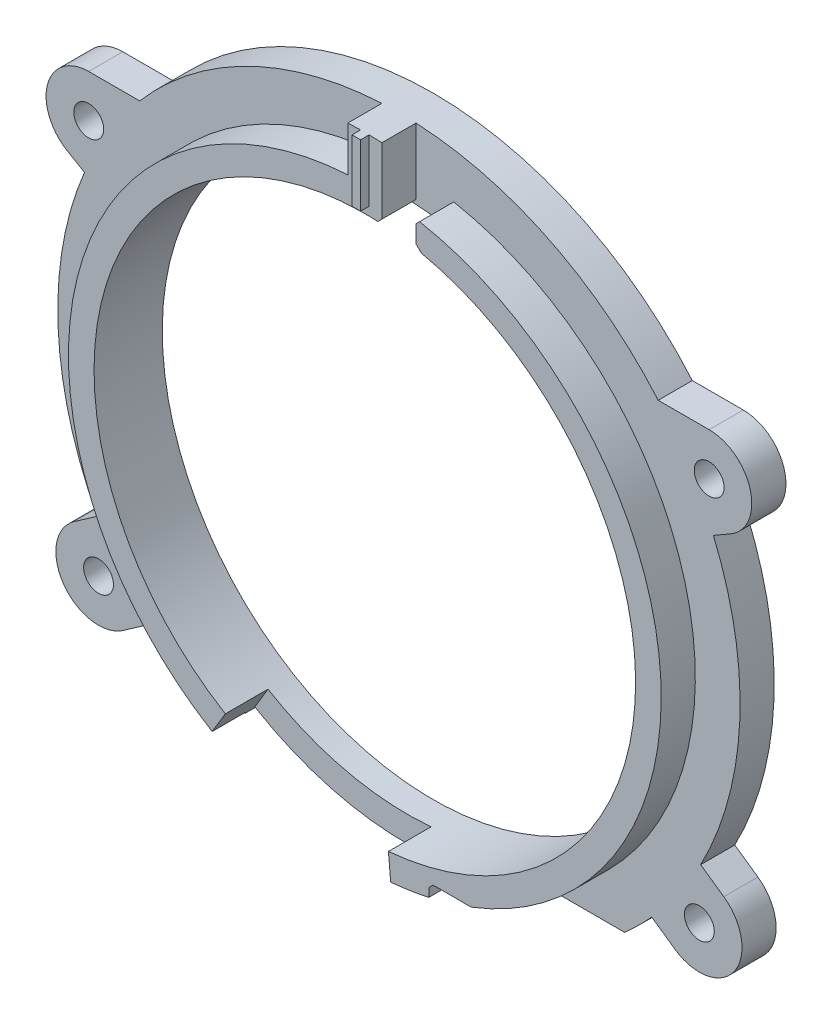
SolidWorks part; units mm, degrees
ref_plane "前视基准面" through (0, 0, 0) normal (0, 0, 1) x (1, 0, 0)
ref_plane "上视基准面" through (0, 0, 0) normal (0, 1, 0) x (1, 0, 0)
ref_plane "右视基准面" through (0, 0, 0) normal (1, 0, 0) x (0, 0, -1)
sketch "草图1" plane through (0, 0, 0) normal (0, 0, 1) x (1, 0, 0)
  circle A0 centre (0, 0) radius 31.75
  circle A1 centre (0, 0) radius 40
  dimension "D1" = 63.5
  dimension "D2" = 80
extrude "凸台-拉伸1" add sketch "草图1" along normal blind 4
sketch "草图2" plane through (0, 0, 4) normal (0, 0, 1) x (1, 0, 0)
  line L0 (0, 0) -> (0, -40) construction
  line L1 (0, 0) -> (-35.2235, -24.6638) construction
  line L2 (-38.0914, -20.568) -> (-35.377, -18.6673)
  line L3 (-32.3557, -28.7595) -> (-29.6412, -26.8589)
  line L4 (0, 0) -> (35.2235, -24.6638) construction
  line L5 (32.3557, -28.7595) -> (29.6412, -26.8589)
  line L6 (38.0914, -20.568) -> (35.377, -18.6673)
  circle A0 centre (0, 0) radius 40 construction
  circle A1 centre (-35.2235, -24.6638) radius 1.75
  arc A2 (-38.0914, -20.568) -> (-32.3557, -28.7595) centre (-35.2235, -24.6638) ccw
  arc A3 (-35.377, -18.6673) -> (-29.6412, -26.8589) centre (0, 0) ccw
  arc A4 (35.377, -18.6673) -> (29.6412, -26.8589) centre (0, 0) cw
  arc A5 (38.0914, -20.568) -> (32.3557, -28.7595) centre (35.2235, -24.6638) cw
  circle A6 centre (35.2235, -24.6638) radius 1.75
  dimension "D1" = 3.5
  dimension "D2" = 10
  dimension "D3" = 43
  dimension "D4" = 55
extrude "凸台-拉伸2" add sketch "草图2" against normal up to surface (4 mm away) up to face at (40, 0, 0)
sketch "草图3" plane through (0, 0, 4) normal (0, 0, 1) x (1, 0, 0)
  line L1 (-26.4575, -30) -> (-18.0278, -30)
  line L2 (18.0278, -30) -> (26.4575, -30)
  circle A2 centre (0, 0) radius 40 construction
  arc A3 (-26.4575, -30) -> (26.4575, -30) centre (0, 0) ccw
  circle A4 centre (0, 0) radius 35 construction
  arc A5 (18.0278, -30) -> (-18.0278, -30) centre (0, 0) cw
  dimension "D2" = 70
  dimension "D1" = 30
extrude "切除-拉伸2" cut sketch "草图3" against normal through all
sketch "草图4" plane through (0, 0, 4) normal (0, 0, 1) x (1, 0, 0)
  line L0 (0, 0) -> (0, 40) construction
  line L1 (-36.3731, 21) -> (0, 0) construction
  line L2 (-36.3731, 26) -> (-30.3974, 26)
  line L3 (-38.8731, 16.6699) -> (-36.8693, 15.513)
  line L4 (36.3731, 21) -> (0, 0) construction
  line L5 (38.8731, 16.6699) -> (36.8693, 15.513)
  line L6 (36.3731, 26) -> (30.3974, 26)
  circle A0 centre (0, 0) radius 40 construction
  circle A1 centre (-36.3731, 21) radius 1.75
  arc A2 (-36.3731, 26) -> (-38.8731, 16.6699) centre (-36.3731, 21) ccw
  arc A3 (-30.3974, 26) -> (-36.8693, 15.513) centre (0, 0) ccw
  arc A4 (30.3974, 26) -> (36.8693, 15.513) centre (0, 0) cw
  arc A5 (36.3731, 26) -> (38.8731, 16.6699) centre (36.3731, 21) cw
  circle A6 centre (36.3731, 21) radius 1.75
  arc M15 (35.377, -18.6673) -> (-35.377, -18.6673) centre (0, 0) ccw
  dimension "D1" = 3.5
  dimension "D2" = 10
  dimension "D3" = 42
  dimension "D4" = 60
extrude "凸台-拉伸3" add sketch "草图4" against normal up to surface (4 mm away) contours L2 A2 L3 A1 M15 | A6 L5 A5 L6 M15 region at (33.3852, 25.8482, 4) region at (-33.3852, 25.8482, 4) up to face at (0, -21.8221, 0)
sketch "草图5" plane through (0, 0, 4) normal (0, 0, -1) x (-1, 0, 0)
  circle A0 centre (0, 0) radius 31.75
  circle A1 centre (0, 0) radius 34.75
  circle A2 centre (0, 0) radius 31.75 construction
  dimension "D1" = 3
extrude "凸台-拉伸4" add sketch "草图5" against normal blind 4
sketch "草图6" plane through (0, 0, 4) normal (0, 0, 1) x (1, 0, 0)
  line L0 (-17.899, -29.7857) -> (-16.3538, -27.2143)
  line L2 (2.7672, -31.6292) -> (3.0287, -34.6178)
  line L3 (0, 0) -> (0, -35) construction
  circle A0 centre (0, 0) radius 31.75 construction
  arc A1 (-16.3538, -27.2143) -> (2.7672, -31.6292) centre (0, 0) ccw
  circle A2 centre (0, 0) radius 34.75 construction
  arc A3 (-17.899, -29.7857) -> (3.0287, -34.6178) centre (0, 0) ccw
  arc A4 (-18.0278, -30) -> (18.0278, -30) centre (0, 0) ccw construction
  dimension "D1" = 5
extrude "切除-拉伸3" cut sketch "草图6" along normal through all
sketch "草图7" plane through (0, 0, 4) normal (0, 0, 1) x (1, 0, 0)
  line L0 (-2, 39.95) -> (-2, 34.6924)
  line L1 (0, 40) -> (0, 0) construction
  line L2 (2, 39.95) -> (2, 34.6924)
  arc A0 (30.3974, 26) -> (-30.3974, 26) centre (0, 0) ccw construction
  arc A1 (3.0287, -34.6178) -> (-17.899, -29.7857) centre (0, 0) ccw construction
  arc A2 (2, 34.6924) -> (-2, 34.6924) centre (0, 0) ccw
  arc A3 (2, 39.95) -> (-2, 39.95) centre (0, 0) ccw
  dimension "D1" = 2
extrude "凸台-拉伸5" add sketch "草图7" along normal up to surface (4 mm away) up to face at (0.1831, 0.7929, 8)
sketch "草图8" plane through (0, 0, 8) normal (0, 0, 1) x (1, 0, 0)
  line L0 (-0.5, 39.9969) -> (-0.5, 31.7461)
  line L1 (0, 0) -> (0, 40) construction
  line L2 (0.5, 39.9969) -> (0.5, 31.7461)
  arc A0 (2, 39.95) -> (-2, 39.95) centre (0, 0) ccw construction
  arc A1 (2.7672, -31.6292) -> (-16.3538, -27.2143) centre (0, 0) ccw construction
  arc A2 (0.5, 31.7461) -> (-0.5, 31.7461) centre (0, 0) ccw
  arc A3 (0.5, 39.9969) -> (-0.5, 39.9969) centre (0, 0) ccw
  dimension "D1" = 0.5
extrude "凸台-拉伸6" add sketch "草图8" along normal blind 1
sketch "草图9" plane through (0, 0, 4) normal (0, 0, 1) x (1, 0, 0)
  line L0 (-17.899, -29.7857) -> (-18.0278, -30)
  line L1 (3.0287, -34.6178) -> (3.0505, -34.8668)
  line L2 (3.0287, -34.6178) -> (2.7672, -31.6292) construction
  line L3 (-16.3538, -27.2143) -> (-17.899, -29.7857) construction
  arc A0 (-18.0278, -30) -> (18.0278, -30) centre (0, 0) ccw construction
  arc A3 (-18.0278, -30) -> (3.0505, -34.8668) centre (0, 0) ccw
  arc A4 (-17.899, -29.7857) -> (3.0287, -34.6178) centre (0, 0) ccw
extrude "切除-拉伸4" cut sketch "草图9" against normal blind 2
sketch "草图10" plane through (0, 0, 4) normal (0, 0, 1) x (1, 0, 0)
  line L4 (3.0287, -34.6178) -> (2.7672, -31.6292)
  line L5 (-16.3538, -27.2143) -> (-17.899, -29.7857)
  line L6 (3.0287, -34.6178) -> (2.7672, -31.6292)
  line L7 (-16.3538, -27.2143) -> (-17.899, -29.7857)
  arc A4 (-17.899, -29.7857) -> (3.0287, -34.6178) centre (0, 0) ccw
  arc A5 (-16.3538, -27.2143) -> (2.7672, -31.6292) centre (0, 0) ccw
  arc A6 (-17.899, -29.7857) -> (3.0287, -34.6178) centre (0, 0) ccw
  arc A7 (-16.3538, -27.2143) -> (2.7672, -31.6292) centre (0, 0) ccw
  dimension "D1" = 0
extrude "切除-拉伸5" cut sketch "草图10" against normal blind 1
chamfer "倒角1" distance 1 angle 45 1 edges at (-7.8179, -33.8592, 2)
sketch "草图11" plane through (0, 0, 8) normal (0, 0, 1) x (1, 0, 0)
  line L1 (7.5, -33.931) -> (12.4817, -33.931)
  line L2 (7.5, -33.931) -> (7.5, -32.431)
  line L3 (7.5, -32.431) -> (12.4817, -32.431)
  line L4 (12.4817, -33.931) -> (12.4817, -32.431)
  arc A0 (3.0287, -34.6178) -> (2, 34.6924) centre (0, 0) ccw construction
  arc A1 (3.0287, -34.6178) -> (2, 34.6924) centre (0, 0) ccw construction
  dimension "D1" = 7.5
  dimension "D2" = 1.5
extrude "切除-拉伸6" cut sketch "草图11" against normal up to surface (4 mm away) up to face at (27.0034, -4.6487, 4)
chamfer "倒角2" distance 0.5 angle 45 1 edges at (7.5, -32.431, 6)
sketch "草图12" plane through (0, 0, 4) normal (0, 0, 1) x (1, 0, 0)
  line L1 (2, 34.6924) -> (6, 34.6924)
  line L2 (2, 34.6924) -> (2, 31.1779)
  line L3 (2, 31.1779) -> (6, 31.1779)
  line L4 (6, 34.6924) -> (6, 31.1779)
  arc A0 (2.7672, -31.6292) -> (0.5, 31.7461) centre (0, 0) ccw construction
  dimension "D1" = 4
extrude "切除-拉伸7" cut sketch "草图12" along normal up to surface (4 mm away) up to face at (-14.2128, 16.8728, 8)
chamfer "倒角3" distance 0.5 angle 45 3 edges at (6, 31.1779, 6) (2, 31.6869, 6) (6, 34.2281, 6) first distance on face at (6, 32.703, 6) first distance on face at (2, 35.8185, 6)
sketch "草图13" plane through (0, 0, 8) normal (0, 0, 1) x (1, 0, 0)
  line L0 (0.5, 31.7461) -> (0.5, 39.9969) construction
  line L1 (-0.5, 31.7461) -> (0.5, 31.7461)
  line L2 (-0.5, 31.7461) -> (-0.5, 32.7461)
  line L3 (-0.5, 32.7461) -> (0.5, 32.7461)
  line L4 (0.5, 31.7461) -> (0.5, 32.7461)
  dimension "D1" = 1
extrude "切除-拉伸8" cut sketch "草图13" along normal up to surface (1 mm away) up to face at (0, 35.8732, 9)
